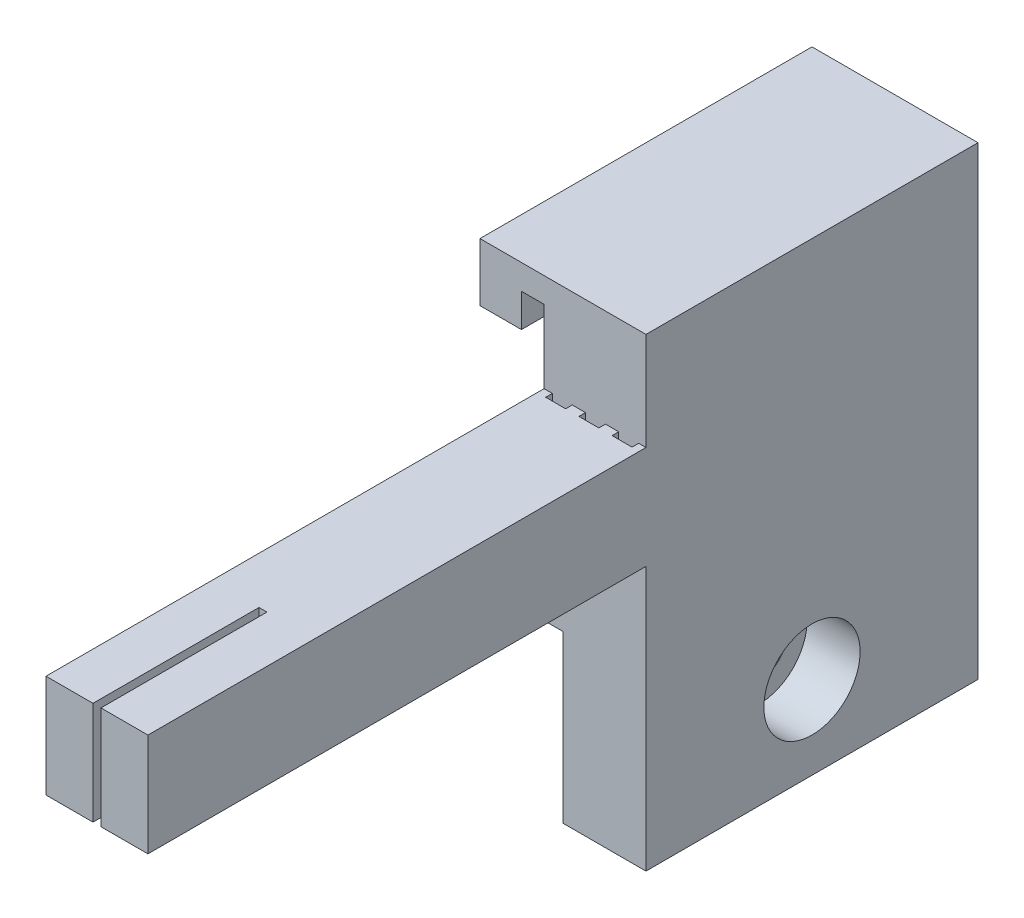
SolidWorks part; units mm, degrees
ref_plane "Front Plane" through (0, 0, 0) normal (0, 0, 1) x (1, 0, 0)
ref_plane "Top Plane" through (0, 0, 0) normal (0, 1, 0) x (1, 0, 0)
ref_plane "Right Plane" through (0, 0, 0) normal (1, 0, 0) x (0, 0, -1)
sketch "Profile" plane through (0, 0, 0) normal (0, 0, 1) x (1, 0, 0)
  line L1 (-6.35, 22.86) -> (6.35, 22.86)
  line L2 (-6.35, 22.86) -> (-6.35, 0)
  line L3 (-6.35, 0) -> (6.35, 0)
  line L4 (6.35, 22.86) -> (6.35, 0)
  line L5 (0, 0) -> (6.35, 0)
  line L6 (0, 0) -> (0, -12.7)
  line L7 (0, -12.7) -> (6.35, -12.7)
  line L8 (6.35, 0) -> (6.35, -12.7)
  point P7 (0, 0)
  dimension "D1" = 22.86
  dimension "D2" = 12.7
  dimension "D3" = 6.35
  dimension "D4" = 12.7
extrude "Boss-Extrude1" add sketch "Profile" along normal mid plane 25.4 contours L4 L1 L2 L3 | L8 L3 L6 L7 region at (0, 11.43, 0) region at (3.175, -6.35, 0)
sketch "ScrewHole" plane through (0, 0, 0) normal (-1, 0, 0) x (0, 0, 1)
  line L0 (12.7, 0) -> (12.7, -12.7) construction
  line L1 (12.7, -12.7) -> (-12.7, -12.7) construction
  circle A0 centre (0, -6.35) radius 2.159
  point P2 (0, 0)
  point P5 (12.7, -6.35)
  point P7 (0, 0)
  point P10 (0, -12.7)
  dimension "D1" = 4.318
extrude "Cut-Extrude1" cut sketch "ScrewHole" against normal through all both
sketch "Sketch3" plane through (6.35, 0, 0) normal (1, 0, 0) x (0, 0, -1)
  circle A0 centre (0, -6.35) radius 2.159 construction
  circle A1 centre (0, -6.35) radius 2.159
  circle A2 centre (0, -6.35) radius 3.683
  dimension "D1" = 7.366
extrude "Cut-Extrude2" cut sketch "Sketch3" against normal blind 4.064
sketch "Sketch4" plane through (0, 0, 12.7) normal (0, 0, 1) x (1, 0, 0)
  line L0 (-6.35, 22.86) -> (-6.35, 0) construction
  line L1 (-1.4478, 20.955) -> (-3.175, 20.955)
  line L2 (-1.4478, 20.955) -> (-1.4478, 1.905)
  line L3 (-1.4478, 1.905) -> (-3.175, 1.905)
  line L4 (-3.175, 20.955) -> (-3.175, 1.905)
  line L5 (-3.175, 18.415) -> (-6.35, 18.415)
  line L6 (-3.175, 18.415) -> (-3.175, 4.445)
  line L7 (-3.175, 4.445) -> (-6.35, 4.445)
  line L8 (-6.35, 18.415) -> (-6.35, 4.445)
  point P10 (-6.35, 11.43)
  point P11 (-6.35, 11.43)
  point P12 (-3.175, 11.43)
  line M10 (-6.35, 22.86) -> (-6.35, 0)
  dimension "D1" = 13.97
  dimension "D2" = 1.7272
  dimension "D3" = 19.05
  dimension "D4" = 3.175
extrude "Cut-Extrude3" cut sketch "Sketch4" against normal through all both and the other way through all contours L7 L4 L5 M10 | L1 L4 L3 L2 region at (-2.3114, 11.43, 12.7) region at (-4.7625, 11.43, 12.7)
sketch "shitty little hall effect plank" plane through (0, 0, 12.7) normal (0, 0, 1) x (1, 0, 0)
  line L0 (-1.4478, 20.955) -> (-1.4478, 1.905) construction
  line L1 (-1.4478, 15.367) -> (6.35, 15.367)
  line L2 (-1.4478, 15.367) -> (-1.4478, 7.493)
  line L3 (-1.4478, 7.493) -> (6.35, 7.493)
  line L4 (6.35, 15.367) -> (6.35, 7.493)
  line L5 (6.35, 22.86) -> (6.35, -12.7) construction
  point P8 (-1.4478, 11.43)
  point P9 (-1.4478, 11.43)
  dimension "D1" = 7.874
extrude "Boss-Extrude2" add sketch "shitty little hall effect plank" along normal blind 38.1
sketch "Sketch6" plane through (0, 15.367, 0) normal (0, 1, 0) x (1, 0, 0)
  line L0 (-1.4478, -50.8) -> (-1.4478, -12.7) construction
  line L1 (-0.8128, -12.7) -> (0.7112, -12.7)
  line L2 (-0.8128, -12.7) -> (-0.8128, -13.208)
  line L3 (-0.8128, -13.208) -> (0.7112, -13.208)
  line L4 (0.7112, -12.7) -> (0.7112, -13.208)
  line L5 (-6.35, -12.7) -> (6.35, -12.7) construction
  line L6 (1.7272, -13.208) -> (3.2512, -13.208)
  line L7 (3.2512, -12.7) -> (3.2512, -13.208)
  line L8 (1.7272, -12.7) -> (3.2512, -12.7)
  line L9 (1.7272, -12.7) -> (1.7272, -13.208)
  line L10 (4.2672, -13.208) -> (5.7912, -13.208)
  line L11 (5.7912, -12.7) -> (5.7912, -13.208)
  line L12 (4.2672, -12.7) -> (5.7912, -12.7)
  line L13 (4.2672, -12.7) -> (4.2672, -13.208)
  line L14 (-0.8128, -13.208) -> (1.7272, -13.208) construction
  line L15 (6.35, -50.8) -> (-1.4478, -50.8) construction
  line L16 (2.1463, -50.8) -> (2.7559, -50.8)
  line L17 (2.1463, -50.8) -> (2.1463, -38.1)
  line L18 (2.1463, -38.1) -> (2.7559, -38.1)
  line L19 (2.7559, -50.8) -> (2.7559, -38.1)
  point P24 (2.4511, -50.8)
  point P25 (2.4511, -50.8)
  dimension "D1" = 0.508
  dimension "D2" = 1.524
  dimension "D3" = 0.635
  dimension "D5" = 2.54
  dimension "D6" = 0.6096
  dimension "D7" = 12.7
  dimension "D4" = 3
extrude "Cut-Extrude4" cut sketch "Sketch6" against normal through all both
